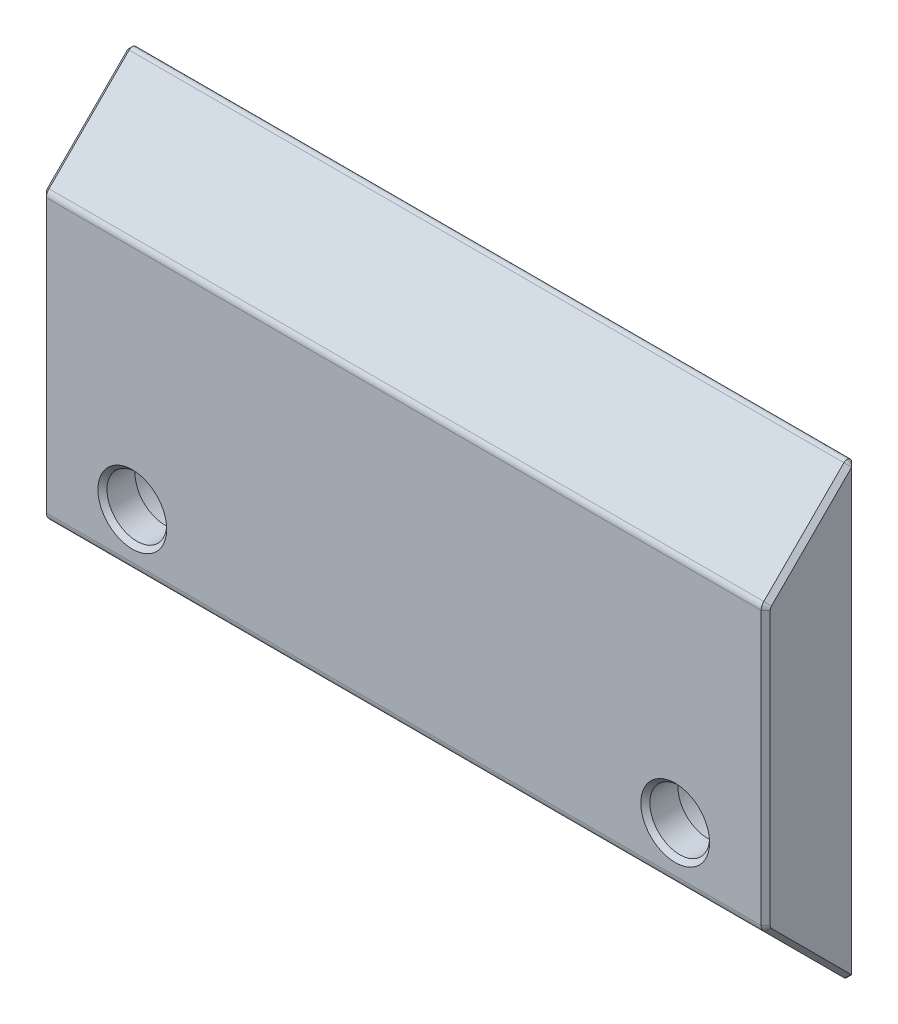
SolidWorks part; units mm, degrees
ref_plane "Top Plane" through (0, 0, 0) normal (0, 0, 1) x (1, 0, 0)
ref_plane "Front Plane" through (0, 0, 0) normal (0, 1, 0) x (1, 0, 0)
ref_plane "Right Plane" through (0, 0, 0) normal (1, 0, 0) x (0, 0, -1)
sketch "Sketch2" plane through (0, 0, 0) normal (1, 0, 0) x (0, 0, -1)
  line L0 (0, 0) -> (0, 51)
  line L1 (0, 51) -> (-10, 41)
  line L2 (-10, 41) -> (-10, 10)
  line L3 (-10, 10) -> (0, 0)
  dimension "D1" = 45
  dimension "D2" = 45
  dimension "D3" = 51
  dimension "D4" = 10
extrude "Boss-Extrude1" add sketch "Sketch2" along normal blind 80
sketch "Sketch4" plane through (0, 0, 0) normal (0, 0, -1) x (-1, 0, 0)
  line L0 (-70, 15.5) -> (-10, 15.5)
  line L1 (-80, 0) -> (-80, 51) construction
  line L2 (-80, 51) -> (0, 51) construction
  point P2 (0, 0)
  point P4 (-73.9821, 16.1549)
  dimension "D1" = 60
  dimension "D2" = 10
  dimension "D3" = 35.5
hole_wizard "CBORE for M6 Hex Socket Head Cap Screw1" positions "Sketch7" profile "Sketch8" counterbore size "M6" standard "DIN" end condition through all
sketch "Sketch7" plane through (0, 0, 0) normal (0, 0, -1) x (-1, 0, 0)
  point P0 (-70, 15.5)
  point P3 (-10, 15.5)
sketch "Sketch8" plane through (70, 15.5, 0) normal (1, 0, 0) x (0, 1, 0)
  line L0 (0, 0) -> (0, 10)
  line L1 (0, 10) -> (3.3, 10)
  line L3 (3.3, 10) -> (3.3, 6.4)
  line L4 (3.3, 6.4) -> (5.5, 6.4)
  line L5 (5.5, 6.4) -> (5.5, 0)
  line L7 (5.5, 0) -> (0, 0)
  line L11 (0, -6.35) -> (0, 107.95) construction
  dimension "Thru Hole Dia." = 6.6
  dimension "Thru Hole Depth" = 10
  dimension "C'Bore Dia." = 11
  dimension "C'Bore Depth" = 6.4
fillet "Fillet1" radius 0.5 2 edges at (40, 51, 0) (40, 0, 0)
fillet "Fillet2" radius 1 2 edges at (40, 41, 10) (40, 10, 10)
chamfer "Chamfer1" distance 0.5 angle 45 18 edges at (0, 10.0315, 9.9239) (0, 5.2803, 5.2803) (0, 0.7452, 0.3087) (0, 25.5, 0) (0, 50.2548, 0.3087) (0, 45.7197, 5.2803) (0, 40.9685, 9.9239) (0, 25.5, 10) (80, 50.2548, 0.3087) (80, 25.5, 0) (80, 0.7452, 0.3087) (80, 5.2803, 5.2803) (80, 10.0315, 9.9239) (80, 25.5, 10) (80, 40.9685, 9.9239) (80, 45.7197, 5.2803) (6.7, 15.5, 10) (66.7, 15.5, 10)
chamfer "Chamfer2" distance 0.5 angle 45 2 edges at (64.5, 15.5, 0) (4.5, 15.5, 0)
